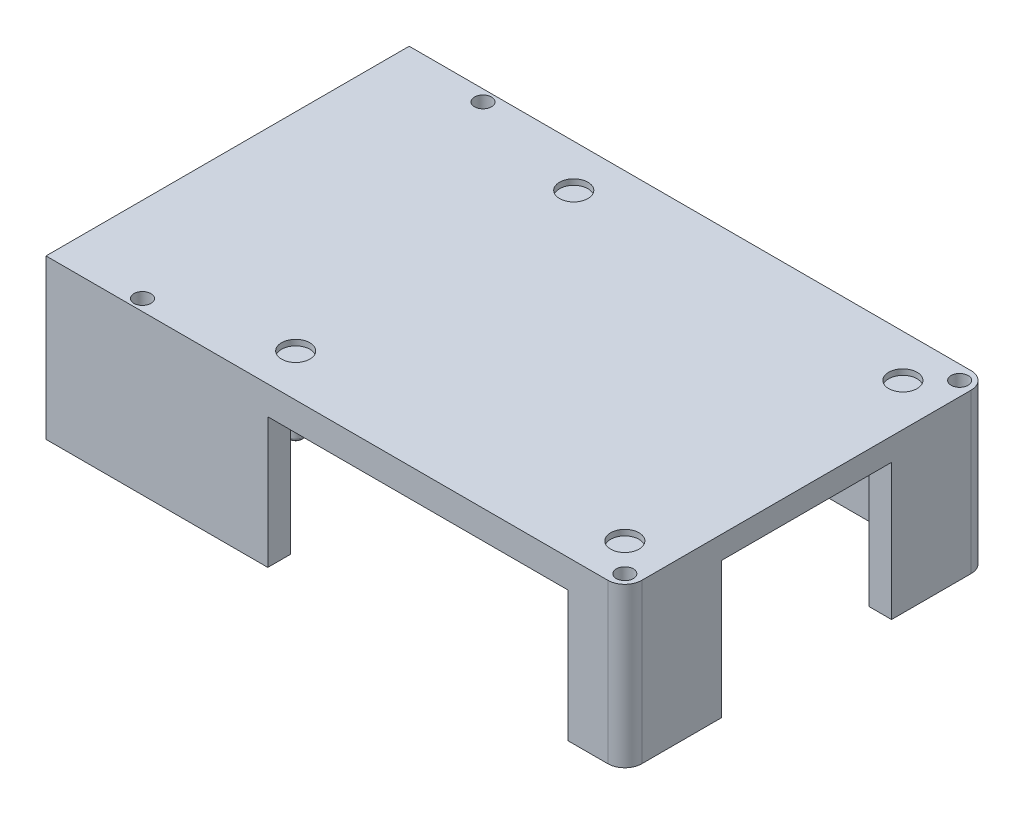
SolidWorks part; units mm, degrees
note: The reader was unsure of these and kept them because the rebuilt part matched: shared geometry of "Sketch1<3>", "Sketch1<4>", "Sketch1<5>", "Sketch1<6>".
ref_plane "Front Plane" through (0, 0, 0) normal (0, 0, 1) x (1, 0, 0)
ref_plane "Top Plane" through (0, 0, 0) normal (0, 1, 0) x (1, 0, 0)
ref_plane "Right Plane" through (0, 0, 0) normal (1, 0, 0) x (0, 0, -1)
sketch "Sketch1" plane through (0, 0, 0) normal (0, 1, 0) x (1, 0, 0)
  line L1 (-29, 24.5) -> (29, 24.5) construction
  line L2 (-29, 24.5) -> (-29, -24.5) construction
  line L3 (-29, -24.5) -> (29, -24.5) construction
  line L4 (29, 24.5) -> (29, -24.5) construction
  line L5 (29.5, -28) -> (-57.5, -28)
  line L6 (32.5, -25) -> (32.5, 25)
  line L7 (29.5, 28) -> (-57.5, 28)
  line L8 (-57.5, -28) -> (-57.5, 28)
  line L9 (33.5, -32) -> (-65.5, -32)
  line L10 (36.5, -29) -> (36.5, 29)
  line L11 (33.5, 32) -> (-65.5, 32)
  line L12 (-65.5, -32) -> (-65.5, 32)
  circle A0 centre (-29, 24.5) radius 1.35
  circle A1 centre (29, 24.5) radius 1.35
  circle A2 centre (29, -24.5) radius 1.35
  circle A3 centre (-29, -24.5) radius 1.35
  arc A4 (36.5, 29) -> (33.5, 32) centre (33.5, 29) ccw
  arc A5 (32.5, 25) -> (29.5, 28) centre (29.5, 25) ccw
  arc A6 (33.5, -32) -> (36.5, -29) centre (33.5, -29) ccw
  arc A7 (29.5, -28) -> (32.5, -25) centre (29.5, -25) ccw
  circle A8 centre (-29, 24.5) radius 2.5
  circle A9 centre (-29, -24.5) radius 2.5
  circle A10 centre (29, -24.5) radius 2.5
  circle A11 centre (29, 24.5) radius 2.5
  point P9 (0, 0)
  point P15 (0, 0)
  point P23 (32.5, 28)
  dimension "D5" = 2.7
  dimension "D6" = 2.7
  dimension "D7" = 2.7
  dimension "D8" = 2.7
  dimension "D16" = 3
  dimension "D18" = 5
  dimension "D19" = 5
  dimension "D20" = 5
  dimension "D21" = 5
  dimension "D1" = 29
  dimension "D2" = 29
  dimension "D3" = 24.5
  dimension "D4" = 49
  dimension "D9" = 90
  dimension "D10" = 3.5
  dimension "D11" = 28
  dimension "D12" = 28
  dimension "D13" = 4
  dimension "D14" = 4
  dimension "D15" = 4
  dimension "D17" = 8
extrude "Boss-Extrude1" add sketch "Sketch1" along normal blind 4 contours L9 A6 L10 A4 L11 L12 A7 L5 L8 L7 A5 L6 | L5 A7 L6 A5 L7 L8 A3 A2 A1 A0 | A3 | A2 | A1 | A0
extrude "Boss-Extrude2" add sketch "Sketch1<3>" against normal blind 4 separate body contours A8 A0 | A9 A3 | A10 A2 | A11 A1
sketch "Sketch1<3>" plane through (0, 0, 0) normal (0, 1, 0) x (1, 0, 0) same geometry as "Sketch1"
sketch "Sketch5" plane through (0, 0, 0) normal (0, -1, 0) x (1, 0, 0)
  circle A0 centre (-29, -24.5) radius 1.35
  circle A1 centre (-29, 24.5) radius 1.35
  circle A2 centre (29, 24.5) radius 1.35
  circle A3 centre (29, -24.5) radius 1.35
  dimension "D1" = 2.7
  dimension "D2" = 2.7
  dimension "D3" = 2.7
  dimension "D4" = 2.7
extrude "Cut-Extrude3" cut sketch "Sketch5" along normal through all both and the other way through all
extrude "Boss-Extrude3" add sketch "Sketch1<4>" along normal blind 3 contours A8 A0 | A11 A1 | A10 A2 | A9 A3
sketch "Sketch1<4>" plane through (0, 0, 0) normal (0, 1, 0) x (1, 0, 0) same geometry as "Sketch1"
extrude "Boss-Extrude4" add sketch "Sketch1<5>" against normal blind 24 contours L9 A6 L10 A4 L11 L12 A7 L5 L8 L7 A5 L6
sketch "Sketch1<5>" plane through (0, 0, 0) normal (0, 1, 0) x (1, 0, 0) same geometry as "Sketch1"
sketch "Sketch7" plane through (-57.5, 0, 0) normal (1, 0, 0) x (0, 0, -1)
  line L0 (-32, 0) -> (32, 0) construction
  line L1 (29, -24) -> (-29, -24)
  line L2 (29, -24) -> (29, 0)
  line L3 (29, 0) -> (-29, 0)
  line L4 (-29, -24) -> (-29, 0)
  line L5 (-29, 4) -> (-29, -24) construction
extrude "Cut-Extrude4" cut sketch "Sketch7" against normal through all
sketch "Sketch8" plane through (32.5, 0, 0) normal (-1, 0, 0) x (0, 0, 1)
  line L0 (25, -24) -> (-25, -24) construction
  line L1 (15, -24) -> (-15, -24)
  line L2 (15, -24) -> (15, 0)
  line L3 (15, 0) -> (-15, 0)
  line L4 (-15, -24) -> (-15, 0)
  line L5 (29, 0) -> (-29, 0) construction
  dimension "D1" = 15
  dimension "D2" = 15
extrude "Cut-Extrude5" cut sketch "Sketch8" against normal through all
sketch "Sketch13" plane through (0, -24, 0) normal (0, -1, 0) x (1, 0, 0)
  line L0 (36.5, 29) -> (36.5, 15) construction
  line L1 (29.5, 28) -> (-26.4131, 28)
  line L2 (29.5, 28) -> (29.5, 32)
  line L3 (29.5, 32) -> (-26.4131, 32)
  line L4 (-26.4131, 28) -> (-26.4131, 32)
  line L5 (33.5, 32) -> (-65.5, 32) construction
  line L6 (26.5, 28) -> (26.5, 32)
  line M13 (-57.5, 28) -> (29.5, 28)
  dimension "D1" = 62.9131
  dimension "D2" = 10
extrude "Cut-Extrude6" cut sketch "Sketch13" against normal blind 23 and the other way blind 1 contours L6 L3 L4 M13
extrude "Boss-Extrude5" add sketch "Sketch1<6>" against normal blind 9 and the other way blind 3 contours A1 | A0 | A3 | A2
sketch "Sketch1<6>" plane through (0, 0, 0) normal (0, 1, 0) x (1, 0, 0) same geometry as "Sketch1"
fillet "Fillet2" radius 0.5 1 edges at (29, -9, 25.85)
fillet "Fillet3" radius 0.5 3 edges at (29, -9, -23.15) (-29, -9, -23.15) (-29, -9, 25.85)
fillet "Fillet4" radius 1 1 edges at (-29, -4, -22)
fillet "Fillet5" radius 1 3 edges at (29, -4, -22) (29, -4, 27) (-29, -4, 27)
sketch "Sketch15" plane through (0, -24, 0) normal (0, -1, 0) x (1, 0, 0)
  line L0 (36.5, -15) -> (36.5, -29) construction
  line L1 (34, -29.5) -> (-50.5, -29.5) construction
  line L2 (34, -29.5) -> (34, 29.5) construction
  line L3 (34, 29.5) -> (-50.5, 29.5) construction
  line L4 (-50.5, -29.5) -> (-50.5, 29.5) construction
  line L5 (33.5, -32) -> (-65.5, -32) construction
  line L6 (26.5, 32) -> (-26.4131, 32) construction
  line L7 (-65.5, -29) -> (-65.5, 29) construction
  line L8 (-26.4131, 32) -> (-65.5, 32) construction
  circle A0 centre (-50.5, 29.5) radius 1.5 construction
  circle A1 centre (-50.5, -29.5) radius 1.5 construction
  circle A2 centre (34, -29.5) radius 1.5
  circle A3 centre (34, 29.5) radius 1.5
  circle A4 centre (-50.5, 30) radius 1.5
  circle A5 centre (-50.5, -30) radius 1.5
  dimension "D5" = 3
  dimension "D6" = 3
  dimension "D7" = 3
  dimension "D8" = 3
  dimension "D9" = 3
  dimension "D11" = 84.5
  dimension "D12" = 3
  dimension "D13" = 2
  dimension "D1" = 2.5
  dimension "D2" = 2.5
  dimension "D3" = 2.5
  dimension "D4" = 15
  dimension "D10" = 2
extrude "Cut-Extrude7" cut sketch "Sketch15" against normal through all both and the other way through all
